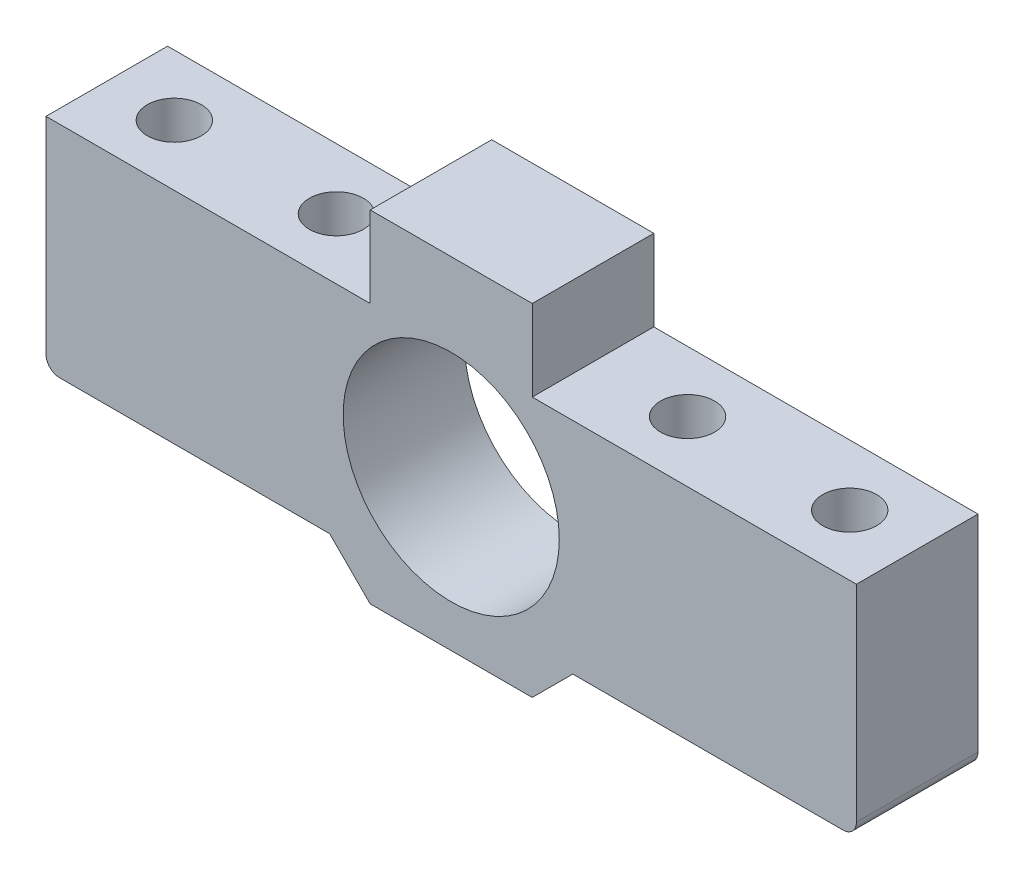
SolidWorks part; units mm, degrees
ref_plane "Front" through (0, 0, 0) normal (0, 0, 1) x (1, 0, 0)
ref_plane "Top" through (0, 0, 0) normal (0, 1, 0) x (1, 0, 0)
ref_plane "Right" through (0, 0, 0) normal (1, 0, 0) x (0, 0, -1)
sketch "Esquisse1" plane through (0, 0, 0) normal (0, 0, 1) x (1, 0, 0)
  line L0 (0, 8.13) -> (60, 8.13) construction
  line L1 (0, 0) -> (60, 0)
  line L2 (0, 0) -> (0, 16.26)
  line L3 (0, 16.26) -> (60, 16.26)
  line L4 (60, 0) -> (60, 16.26)
  circle A0 centre (30, 8.13) radius 8
  dimension "D3" = 16
  dimension "D1" = 16.26
  dimension "D2" = 60
extrude "Boss.-Extru.1" add sketch "Esquisse1" along normal blind 9
sketch "Esquisse2" plane through (0, 0, 9) normal (0, 0, 1) x (1, 0, 0)
  line L0 (60, 16.26) -> (0, 16.26) construction
  line L1 (24, 16.26) -> (36, 16.26)
  line L2 (24, 16.26) -> (24, 22.26)
  line L3 (24, 22.26) -> (36, 22.26)
  line L4 (36, 16.26) -> (36, 22.26)
  line L5 (30, 22.26) -> (30, 0) construction
  line L6 (0, 0) -> (60, 0) construction
  dimension "D1" = 12
  dimension "D2" = 6
extrude "Boss.-Extru.2" add sketch "Esquisse2" against normal up to vertex (9 mm away) up to point (60, 16.26, 0)
sketch "Esquisse3" plane through (0, 0, 9) normal (0, 0, 1) x (1, 0, 0)
  line L0 (0, 0) -> (60, 0) construction
  line L1 (24, 0) -> (36, 0)
  line L2 (24, 0) -> (24, -3)
  line L3 (24, -3) -> (36, -3)
  line L4 (36, 0) -> (36, -3)
  line L5 (30, -3) -> (30, 8.13) construction
  dimension "D1" = 3
  dimension "D2" = 12
extrude "Boss.-Extru.3" add sketch "Esquisse3" against normal up to vertex (9 mm away) up to point (0, 0, 0)
chamfer "Chanfrein2" distance 3 angle 45 2 edges at (36, 0, 4.5) (24, 0, 4.5)
sketch "Esquisse4" plane through (0, 0, 0) normal (0, -1, 0) x (1, 0, 0)
  line L0 (0, 4.5) -> (17, 4.5) construction
  line L1 (0, 9) -> (0, 0) construction
  line L2 (30, 0) -> (30, 9) construction
  line L3 (24, 0) -> (36, 0) construction
  line L4 (24, 9) -> (36, 9) construction
  line L5 (60, 4.5) -> (43, 4.5) construction
  circle A0 centre (17, 4.5) radius 2
  circle A1 centre (5, 4.5) radius 2
  circle A2 centre (55, 4.5) radius 2
  circle A3 centre (43, 4.5) radius 2
  dimension "D1" = 4
  dimension "D2" = 12
  dimension "D3" = 26
extrude "Enlèv. mat.-Extru.1" cut sketch "Esquisse4" against normal through all
fillet "Congé1" radius 1 2 edges at (0, 0, 4.5) (60, 0, 4.5)
